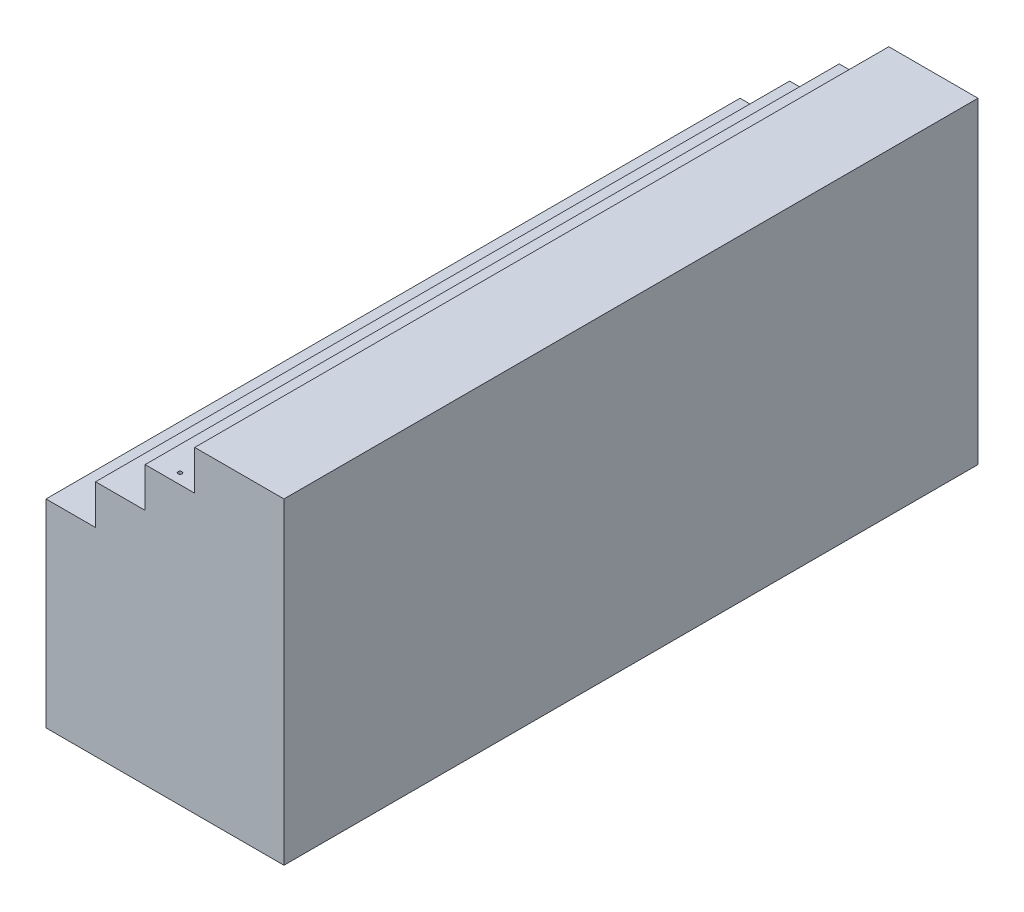
SolidWorks part; units mm, degrees
material "granite"
ref_plane "Front Plane" through (0, 0, 0) normal (0, 0, 1) x (1, 0, 0)
ref_plane "Top Plane" through (0, 0, 0) normal (0, 1, 0) x (1, 0, 0)
ref_plane "Right Plane" through (0, 0, 0) normal (1, 0, 0) x (0, 0, -1)
sketch "Эскиз1" plane through (0, 0, 0) normal (0, 1, 0) x (1, 0, 0)
  line L0 (1140, 3500) -> (1140, 0)
  line L1 (0, 0) -> (1200, 0)
  line L2 (0, 0) -> (0, 3500)
  line L3 (0, 3500) -> (1200, 3500)
  line L4 (1200, 0) -> (1200, 3500)
  line L5 (250, 3500) -> (250, 0)
  line L6 (500, 3500) -> (500, 0)
  line L7 (750, 3500) -> (750, 0)
  dimension "D1" = 250
  dimension "D2" = 250
  dimension "D3" = 250
  dimension "D4" = 60
  dimension "D5" = 3500
  dimension "D6" = 1200
extrude "Бобышка-Вытянуть1" add sketch "Эскиз1" along normal blind 1000 contours L5 L3 L2 L1 region at (125, 0, -1750)
extrude "Бобышка-Вытянуть2" add sketch "Эскиз1<3>" along normal blind 1200 contours L6 L3 L5 L1 region at (375, 0, -1750)
sketch "Эскиз1<3>" plane through (0, 0, 0) normal (0, 1, 0) x (1, 0, 0) same geometry as "Эскиз1"
extrude "Бобышка-Вытянуть3" add sketch "Эскиз1<4>" along normal blind 1400 contours L7 L3 L6 L1 region at (625, 0, -1750)
sketch "Эскиз1<4>" plane through (0, 0, 0) normal (0, 1, 0) x (1, 0, 0) same geometry as "Эскиз1"
extrude "Бобышка-Вытянуть4" add sketch "Эскиз1<5>" along normal blind 1600 contours L3 L7 L1 L0 region at (945, 0, -1750)
sketch "Эскиз1<5>" plane through (0, 0, 0) normal (0, 1, 0) x (1, 0, 0) same geometry as "Эскиз1"
extrude "Бобышка-Вытянуть5" add sketch "Эскиз1<6>" along normal blind 1600 contours L1 L4 L3 L0 region at (1170, 0, -1750)
sketch "Эскиз1<6>" plane through (0, 0, 0) normal (0, 1, 0) x (1, 0, 0) same geometry as "Эскиз1"
sketch "Эскиз2" plane through (0, 1400, 0) normal (0, 1, 0) x (1, 0, 0)
  circle A0 centre (625, 3357.1521) radius 10
  circle A1 centre (625, 3243.137) radius 10
  circle A2 centre (625, 3145.793) radius 10
  circle A3 centre (625, 3016.4639) radius 10
  circle A4 centre (625, 2886.8924) radius 10
  circle A6 centre (625, 2776.185) radius 10
  circle A7 centre (625, 2652.1125) radius 10
  circle A8 centre (625, 2528.6152) radius 10
  circle A9 centre (625, 2426.8665) radius 10
  circle A11 centre (625, 2323.054) radius 10
  circle A12 centre (625, 2236.3631) radius 12.336
extrude "Вырез-Вытянуть1" cut sketch "Эскиз2" against normal blind 230
sketch "Эскиз10" plane through (0, 1400, 0) normal (0, 1, 0) x (1, 0, 0)
  circle A0 centre (632.852, 2116.6173) radius 10
  circle A1 centre (632.852, 2002.6022) radius 10
  circle A2 centre (632.852, 1905.2582) radius 10
  circle A3 centre (632.852, 1775.9291) radius 10
  circle A4 centre (632.852, 1646.3576) radius 10
  circle A6 centre (632.852, 1535.6502) radius 10
  circle A7 centre (632.852, 1411.5777) radius 10
  circle A8 centre (632.852, 1288.0804) radius 10
  circle A9 centre (632.852, 1186.3317) radius 10
  circle A11 centre (632.852, 1082.5192) radius 10
  circle A12 centre (632.852, 995.8283) radius 12.336
extrude "Вырез-Вытянуть8" cut sketch "Эскиз10" against normal blind 230
sketch "Эскиз16" plane through (0, 1400, 0) normal (0, 1, 0) x (1, 0, 0)
  circle A0 centre (623.6728, 880.7229) radius 10
  circle A1 centre (623.6728, 766.7078) radius 10
  circle A2 centre (623.6728, 669.3637) radius 10
  circle A3 centre (623.6728, 540.0346) radius 10
  circle A4 centre (623.6728, 410.4632) radius 10
  circle A6 centre (623.6728, 299.7558) radius 10
  circle A7 centre (623.6728, 175.6833) radius 10
  circle A8 centre (623.6728, 52.186) radius 10
  circle A9 centre (623.6728, -49.5627) radius 10
  circle A11 centre (623.6728, -153.3752) radius 10
  circle A12 centre (623.6728, -240.0661) radius 12.336
extrude "Вырез-Вытянуть14" cut sketch "Эскиз16" against normal blind 230
